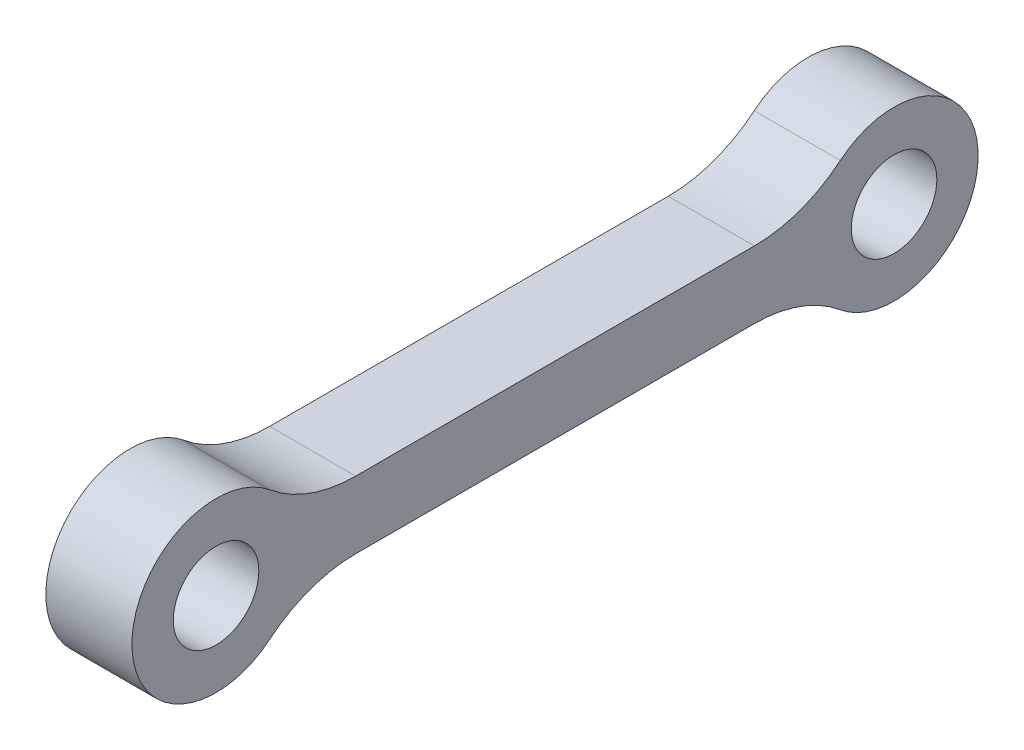
SolidWorks part; units mm, degrees
material "6061-T6 (SS)"
ref_plane "Front Plane" through (0, 0, 0) normal (0, 0, 1) x (1, 0, 0)
ref_plane "Top Plane" through (0, 0, 0) normal (0, 1, 0) x (1, 0, 0)
ref_plane "Right Plane" through (0, 0, 0) normal (1, 0, 0) x (0, 0, -1)
sketch "Sketch1" plane through (0, 0, 0) normal (1, 0, 0) x (0, 0, -1)
  line L3 (3.6374, 1.5875) -> (28.3626, 1.5875)
  line L5 (3.6374, -1.5875) -> (28.3626, -1.5875)
  circle A2 centre (0, 0) radius 2.0193
  circle A3 centre (32, 0) radius 2.0193
  arc A4 (3.6374, 1.5875) -> (3.6374, -1.5875) centre (0, 0) ccw
  arc A5 (28.3626, -1.5875) -> (28.3626, 1.5875) centre (32, 0) ccw
  point P0 (0, 0)
  point P7 (0, 0)
  point P12 (0, 0)
  point P13 (0, 0)
  point P14 (32.6551, 5.2111)
  point P15 (0, 0)
  dimension "D1" = 32
  dimension "D3" = 4.0386
  dimension "D2" = 7.9375
  dimension "D4" = 3.175
extrude "Boss-Extrude1" add sketch "Sketch1" along normal blind 4.064
fillet "Fillet1" radius 6.35 4 edges at (2.032, 1.5875, -28.3626) (2.032, -1.5875, -28.3626) (2.032, -1.5875, -3.6374) (2.032, 1.5875, -3.6374)
